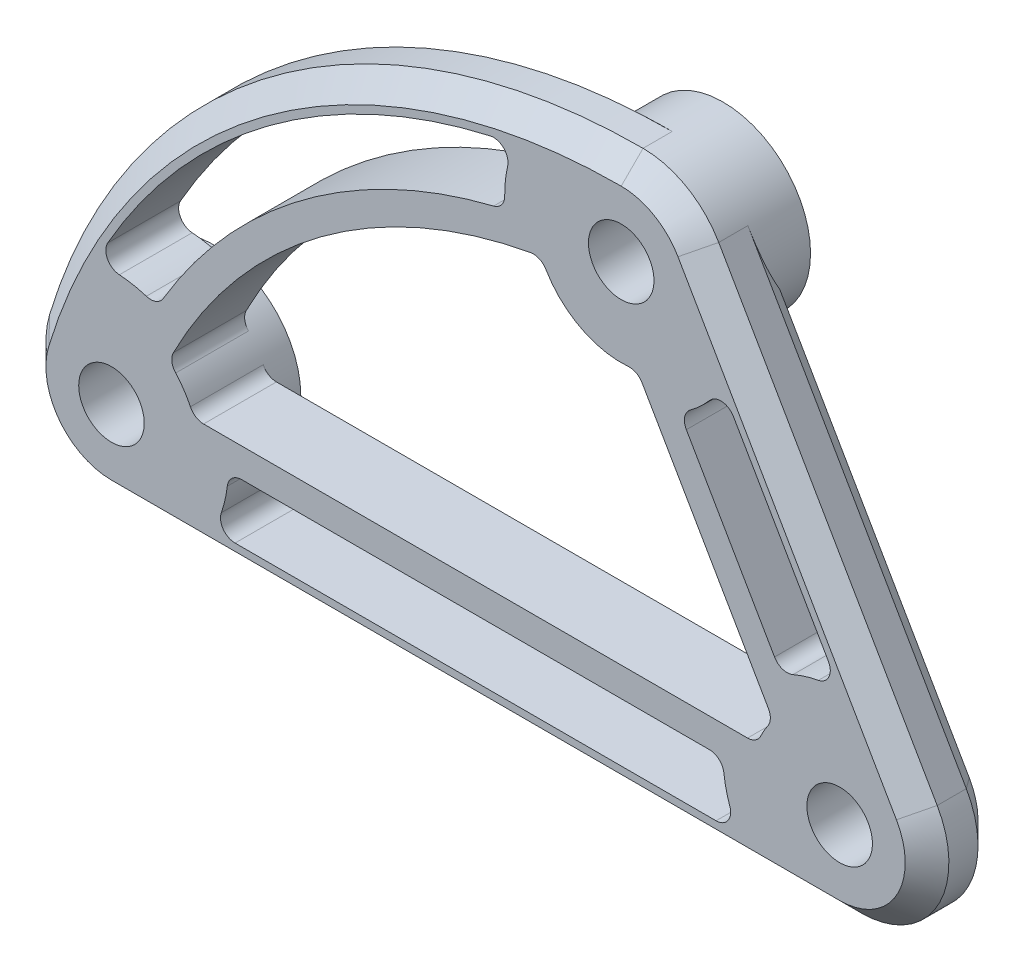
SolidWorks part; units mm, degrees
ref_plane "Front Plane" through (0, 0, 0) normal (0, 0, 1) x (1, 0, 0)
ref_plane "Top Plane" through (0, 0, 0) normal (0, 1, 0) x (1, 0, 0)
ref_plane "Right Plane" through (0, 0, 0) normal (1, 0, 0) x (0, 0, -1)
sketch "Sketch1" plane through (0, 0, 0) normal (0, 0, 1) x (1, 0, 0)
  line L0 (-15, 25.9808) -> (0, 0) construction
  line L1 (0, 0) -> (-50, 0) construction
  line L2 (-15, 25.9808) -> (38.9834, 25.9808) construction
  line L3 (-16.1438, 23.9618) -> (-3.4641, 2)
  line L4 (-3.4641, 2) -> (-47.1932, 2)
  line L5 (-9.8038, 28.9808) -> (5.1962, 3)
  line L6 (0, -6) -> (-50, -6)
  line L7 (10.3923, -6) -> (-57.3179, -6) construction
  line L8 (-11.4503, 31.8325) -> (10.3923, -6) construction
  line L9 (0, 0) -> (0, -53.62) construction
  line L10 (0, 0) -> (-38.3022, -32.1394) construction
  arc A0 (-50, 0) -> (-15, 25.9808) centre (-15, -10.5848) cw construction
  circle A1 centre (0, 0) radius 6
  circle A2 centre (-50, 0) radius 6
  circle A3 centre (-15, 25.9808) radius 6
  arc A4 (-47.1932, 2) -> (-16.1438, 23.9618) centre (-15, -10.5848) cw
  arc A5 (-55.7431, 1.7368) -> (-15, 31.9808) centre (-15, -10.5848) cw
  arc A6 (-57.3179, -6) -> (-11.4503, 31.8325) centre (-15, -10.5848) cw construction
  circle A7 centre (-38.3022, -32.1394) radius 6
  arc A8 (-50, 0) -> (-38.3022, -32.1394) centre (-22.691, -8.2588) ccw construction
  arc A9 (-49.1252, -6) -> (-41.4427, -27.0269) centre (-22.691, -8.2588) ccw
  arc A10 (-55.7431, 1.7368) -> (-41.5853, -37.1615) centre (-22.691, -8.2588) ccw
  arc A11 (-48.0856, -0.5789) -> (-37.2079, -30.4653) centre (-22.691, -8.2588) ccw construction
  dimension "D4" = 12
  dimension "D1" = 60
  dimension "D2" = 30
  dimension "D3" = 50
  dimension "D7" = 50
  dimension "D8" = 50
  dimension "D5" = 2
  dimension "D6" = 6
  dimension "D9" = 2
  dimension "D10" = 6
extrude "Boss-Extrude1" add sketch "Sketch1" along normal blind 5 contours L4 A4 A2 | A5 A2 A4 A3 | A4 L4 A2 | A2 L6 A1 L4 | A1 L3 L4 | A3 L3 A1 L5 | L3 A1 L4 | A3 A4 L3 | A4 A3 L3 region at (-14.6616, 26.6108, 0) region at (-17.1102, 22.0519, 0) region at (-5.5539, 14.1139, 0) region at (-37.1588, 19.2665, 0) region at (0.0925, -0.0534, 0) region at (-4.5992, 2.6553, 0) region at (-50.1572, -0.1088, 0) region at (-45.8082, 2.9003, 0) region at (-25, -2.1235, 0)
sketch "Sketch2" plane through (0, 0, 0) normal (0, 0, -1) x (-1, 0, 0)
  line L7 (0, -4) -> (50, -4)
  line L8 (11.5359, 27.9808) -> (-3.4641, 2)
  line L9 (0, -6) -> (50, -6)
  line L10 (9.8038, 28.9808) -> (-5.1962, 3)
  line L11 (5.2915, -6) -> (44.7085, -6)
  line L12 (7.1581, 24.3982) -> (-2.5504, 7.5826)
  line L19 (12.1716, 21.0818) -> (2.8284, 4.899)
  line L20 (12.1716, 21.0818) -> (2.8284, 4.899)
  line L21 (9.8038, 28.9808) -> (-5.1962, 3) construction
  line L22 (5.6569, 0) -> (44.3431, 0)
  line L23 (5.6569, 0) -> (44.3431, 0)
  line L24 (0, -6) -> (50, -6) construction
  arc A0 (4.4721, -4) -> (-1.228, 5.873) centre (0, 0) ccw
  circle A1 centre (15, 25.9808) radius 6
  circle A2 centre (50, 0) radius 6
  arc A3 (53.7277, 7.0784) -> (44.7085, -6) centre (50, 0) ccw
  arc A4 (7.1581, 24.3982) -> (20.6963, 31.5979) centre (15, 25.9808) ccw
  arc A5 (5.2915, -6) -> (-2.5504, 7.5826) centre (0, 0) ccw
  circle A6 centre (15, 25.9808) radius 8 construction
  circle A7 centre (50, 0) radius 8 construction
  arc A8 (55.7431, 1.7368) -> (15, 31.9808) centre (15, -10.5848) ccw construction
  arc A12 (-3.4641, 2) -> (0, -4) centre (0, 0) ccw
  arc A13 (50, -4) -> (53.8287, 1.1579) centre (50, 0) ccw
  arc A14 (53.8287, 1.1579) -> (15, 29.9808) centre (15, -10.5848) ccw
  arc A15 (15, 29.9808) -> (11.5359, 27.9808) centre (15, 25.9808) ccw
  arc A16 (-5.1962, 3) -> (0, -6) centre (0, 0) ccw
  arc A17 (50, -6) -> (55.7431, 1.7368) centre (50, 0) ccw
  arc A18 (55.7431, 1.7368) -> (15, 31.9808) centre (15, -10.5848) ccw
  arc A19 (15, 31.9808) -> (9.8038, 28.9808) centre (15, 25.9808) ccw
  arc A21 (50, -6) -> (55.7431, 1.7368) centre (50, 0) ccw
  arc A22 (53.7277, 7.0784) -> (20.6963, 31.5979) centre (15, -10.5848) ccw
  arc A23 (15, 31.9808) -> (9.8038, 28.9808) centre (15, 25.9808) ccw
  circle A27 centre (0, 0) radius 8 construction
  arc A28 (47.878, 5.4175) -> (20.7998, 25.5179) centre (15, -10.5848) ccw
  arc A29 (47.878, 5.4175) -> (20.7998, 25.5179) centre (15, -10.5848) ccw
  circle A30 centre (0, 0) radius 6 construction
  arc A31 (-5.1962, 3) -> (0, -6) centre (0, 0) ccw construction
  dimension "D1" = 2
  dimension "D2" = 0
  dimension "D3" = 2
  dimension "D4" = 2
  dimension "D5" = 2
  dimension "D6" = 2
extrude "Cut-Extrude1" cut sketch "Sketch2" against normal blind 10 contours A5 L20 A4 L8 | A5 L7 A3 L23 | A29 A3 A14 A4 region at (-25, -2.0203, 0) region at (-5.7265, 14.0143, 0) region at (-37.3046, 19.4629, 0)
fillet "Fillet1" radius 1 18 edges at (-22.2677, 29.3244, 2.5) (-51.0967, 7.9245, 2.5) (-46.8604, 7.3582, 2.5) (-22.952, 25.1056, 2.5) (-42, 0, 2.5) (-43.0718, -4, 2.5) (-6.9282, -4, 2.5) (-8, 0, 2.5) (-8.0718, 21.9808, 2.5) (-4, 6.9282, 2.5) (0, 8, 2.5) (-13.9036, 20.0818, 2.5) (-20.4825, 23.5432, 2.5) (-46.0797, 4.5422, 2.5) (-44.3431, 2, 2.5) (-5.6569, 2, 2.5) (-4.5605, 3.899, 2.5) (-11, 19.0526, 2.5)
extrude "Boss-Extrude3" add sketch "Sketch1<4>" against normal blind 2 contours A3 A4 L3 | A4 A3 L3 | A4 L4 A2 | L4 A4 A2 region at (-14.6616, 26.6108, 0) region at (-17.1102, 22.0519, 0) region at (-50.1572, -0.1088, 0) region at (-45.8082, 2.9003, 0)
sketch "Sketch1<4>" plane through (0, 0, 0) normal (0, 0, 1) x (1, 0, 0) same geometry as "Sketch1"
chamfer "Chamfer1" distance 1.5 angle 45 10 edges at (-2.3038, 15.9904, 5) (-12, 31.1769, 5) (5.1962, -3, 5) (-40.3707, 23.5934, 5) (-25, -6, 5) (-54.8177, -3.5762, 5) (-25, -6, 0) (5.1962, -3, 0) (-2.3038, 15.9904, 0) (-40.3707, 23.5934, 0)
hole_wizard "M4 Clearance Hole1" positions "Sketch3" profile "Sketch4" hole size "M4" standard "ANSI Metric" end condition through all
sketch "Sketch3" plane through (0, 0, -2) normal (0, 0, -1) x (-1, 0, 0)
  point P0 (0, 0)
  point P3 (15, 25.9808)
  point P6 (50, 0)
sketch "Sketch4" plane through (0, 0, -2) normal (1, 0, 0) x (0, 1, 0)
  line L0 (0, 0) -> (0, 7)
  line L1 (0, 7) -> (2.25, 7)
  line L2 (2.25, 7) -> (2.25, 0)
  line L5 (2.25, 0) -> (0, 0)
  line L11 (0, -6.35) -> (0, 107.95) construction
  dimension "Thru Hole Dia." = 4.5
  dimension "Thru Hole Depth" = 7
